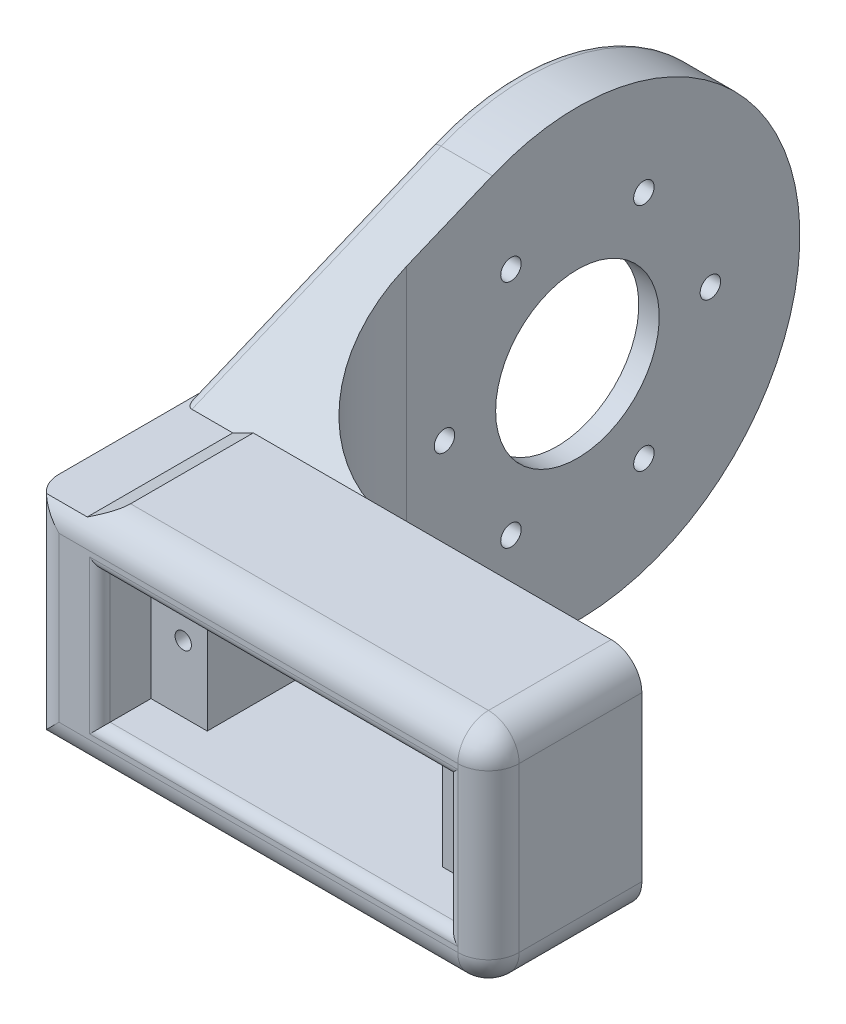
SolidWorks part; units mm, degrees
note: The reader was unsure of these and kept them because the rebuilt part matched: shared geometry of "Эскиз1<5>", "Эскиз9<5>".
ref_plane "Спереди" through (0, 0, 0) normal (0, 0, 1) x (1, 0, 0)
ref_plane "Сверху" through (0, 0, 0) normal (0, 1, 0) x (1, 0, 0)
ref_plane "Справа" through (0, 0, 0) normal (1, 0, 0) x (0, 0, -1)
other "Configuration Table"
sketch "Эскиз1" plane through (0, 0, 0) normal (0, 0, 1) x (1, 0, 0)
  line L0 (11.5, -6.5) -> (17, -6.5)
  line L1 (11.5, -6.5) -> (-11.5, -6.5)
  line L2 (11.5, -6.5) -> (11.5, 6.5)
  line L3 (11.5, 6.5) -> (-11.5, 6.5)
  line L4 (-11.5, -6.5) -> (-11.5, 6.5)
  line L5 (11.5, -6.5) -> (-11.5, 6.5) construction
  line L6 (11.5, 6.5) -> (-11.5, -6.5) construction
  line L7 (17, -11) -> (-17, -11)
  line L8 (17, -11) -> (17, 11)
  line L9 (17, 11) -> (-17, 11)
  line L10 (-17, -11) -> (-17, 11)
  line L11 (17, -11) -> (-17, 11) construction
  line L12 (17, 11) -> (-17, -11) construction
  line L13 (-19, -10) -> (-19, 10)
  line L14 (17, -11) -> (21, -11)
  line L15 (17, -11) -> (17, 11)
  line L16 (17, 11) -> (21, 11)
  line L17 (21, -11) -> (21, 11)
  line L18 (-19, 10) -> (-17, 11)
  line L19 (-19, -10) -> (-17, -11)
  line L20 (0, 0) -> (37.2271, 0) construction
  line L21 (17, -6.5) -> (11.5, -6.5)
  line L22 (-19, -10) -> (-24, -10)
  line L23 (-19, -10) -> (-19, 10)
  line L24 (-19, 10) -> (-24, 10)
  line L25 (-24, -10) -> (-24, 10)
  line L26 (11.5, 6.5) -> (17, 6.5)
  line L27 (-11.5, -6.5) -> (-17, -6.5)
  line L28 (-11.5, 6.5) -> (-17, 6.5)
  point P0 (0, 0)
  point P6 (0, 0)
  dimension "D1" = 23
  dimension "D2" = 13
  dimension "D3" = 22
  dimension "D4" = 34
  dimension "D5" = 2
  dimension "D6" = 20
  dimension "D7" = 5
  dimension "D8" = 4
extrude "Бобышка-Вытянуть1" add sketch "Эскиз1" along normal blind 10
extrude "Бобышка-Вытянуть2" add sketch "Эскиз1<5>" along normal blind 5 from surface at 10 contours L28 L3 L26 L15 L9 L10 | L14 L17 L16 L15 L8 | L1 L27 L10 L7 L8 L0 | L13 L19 L10 L18 | L25 L22 L13 L24 starting at face at (0, 0, 10)
sketch "Эскиз1<5>" plane through (0, 0, 0) normal (0, 0, 1) x (1, 0, 0) same geometry as "Эскиз1"
sketch "Эскиз9" plane through (-24, 0, 0) normal (-1, 0, 0) x (0, 0, 1)
  line L0 (-24.3786, -20.0952) -> (0, -10)
  line L1 (0, 10) -> (-24.3786, 20.0952)
  line L4 (0, 10) -> (0, -10)
  line L5 (0, -10) -> (15, -10)
  line L6 (15, -10) -> (15, 10)
  line L7 (15, 10) -> (0, 10)
  line L8 (0, 10) -> (0, -10)
  line L9 (0, -10) -> (15, -10)
  line L10 (15, -10) -> (15, 10)
  line L11 (15, 10) -> (0, 10)
  circle A0 centre (-32.7, 0) radius 18.75
  circle A1 centre (-32.7, 0) radius 21.75
  circle A2 centre (-32.7, 0) radius 8
  line M9 (0, 10) -> (0, -10)
  dimension "D1" = 37.5
  dimension "D2" = 3
  dimension "D4" = 16
  dimension "D5" = 32.7
  dimension "D3" = 0
extrude "Бобышка-Вытянуть4" add sketch "Эскиз9" against normal blind 6 contours A1 A0 | A1 L0 L1 M9 | A0 A2
extrude "Вырез-Вытянуть4" cut sketch "Эскиз9<5>" against normal blind 4 contours A0
sketch "Эскиз9<5>" plane through (-24, 0, 0) normal (-1, 0, 0) x (0, 0, 1) same geometry as "Эскиз9"
fillet "Скругление6" radius 1 4 edges at (-24, 15.0476, -12.1893) (-24, -15.0476, -12.1893) (-24, 0, -54.45) (-24, 0, -13.95)
sketch "Эскиз10" plane through (-20, 0, 0) normal (-1, 0, 0) x (0, 0, 1)
  line L0 (-32.7, 0) -> (-45.6985, 0) construction
  circle A9 centre (-45.6985, 0) radius 1
  circle A12 centre (-39.198, 11.2578) radius 1
  circle A13 centre (-26.1983, 11.2571) radius 1
  circle A14 centre (-19.699, -0.0014) radius 1
  circle A15 centre (-26.1995, -11.2592) radius 1
  circle A16 centre (-39.1993, -11.2585) radius 1
  point P16 (-32.6988, -0.0007)
  dimension "D1" = 2
  dimension "D2" = 12.9985
  dimension "D3" = 6
extrude "Вырез-Вытянуть5" cut sketch "Эскиз10" against normal blind 4
fillet "Скругление3" radius 1 4 edges at (17, 0, 15) (0, 6.5, 15) (-17, 0, 15) (0, -6.5, 15)
hole_wizard "Отверстие с зазором M1.41" positions "Эскиз5" profile "Эскиз6" hole size "M1.4" standard "ISO"
sketch "Эскиз5" plane through (0, 0, 10) normal (0, 0, 1) x (1, 0, 0)
  line L0 (0, 0) -> (0, 3.4014) construction
  point P0 (13.85, 0)
  point P3 (-13.85, 0)
  dimension "D1" = 13.85
sketch "Эскиз6" plane through (13.85, 0, 10) normal (1, 0, 0) x (0, -1, 0)
  line L0 (0, 0) -> (0, 5)
  line L1 (0, 5) -> (0.8, 4.5193)
  line L2 (0.8, 4.5193) -> (0.8, 0)
  line L5 (0.8, 0) -> (0, 0)
  line L10 (0, 5) -> (-0.8, 4.5193) construction
  line L11 (0, -6.35) -> (0, 107.95) construction
  dimension "Диаметр отверстия" = 1.6
  dimension "Глубина отверстия" = 5
  dimension "Угол заточки сверла" = 118
fillet "Скругление7" radius 3 6 edges at (21, 0, 15) (2, -11, 15) (2, 11, 15) (21, 11, 7.5) (21, -11, 7.5) (-24, 0, 15)
fillet "Скругление8" radius 16 1 edges at (-18, 0, 0)
